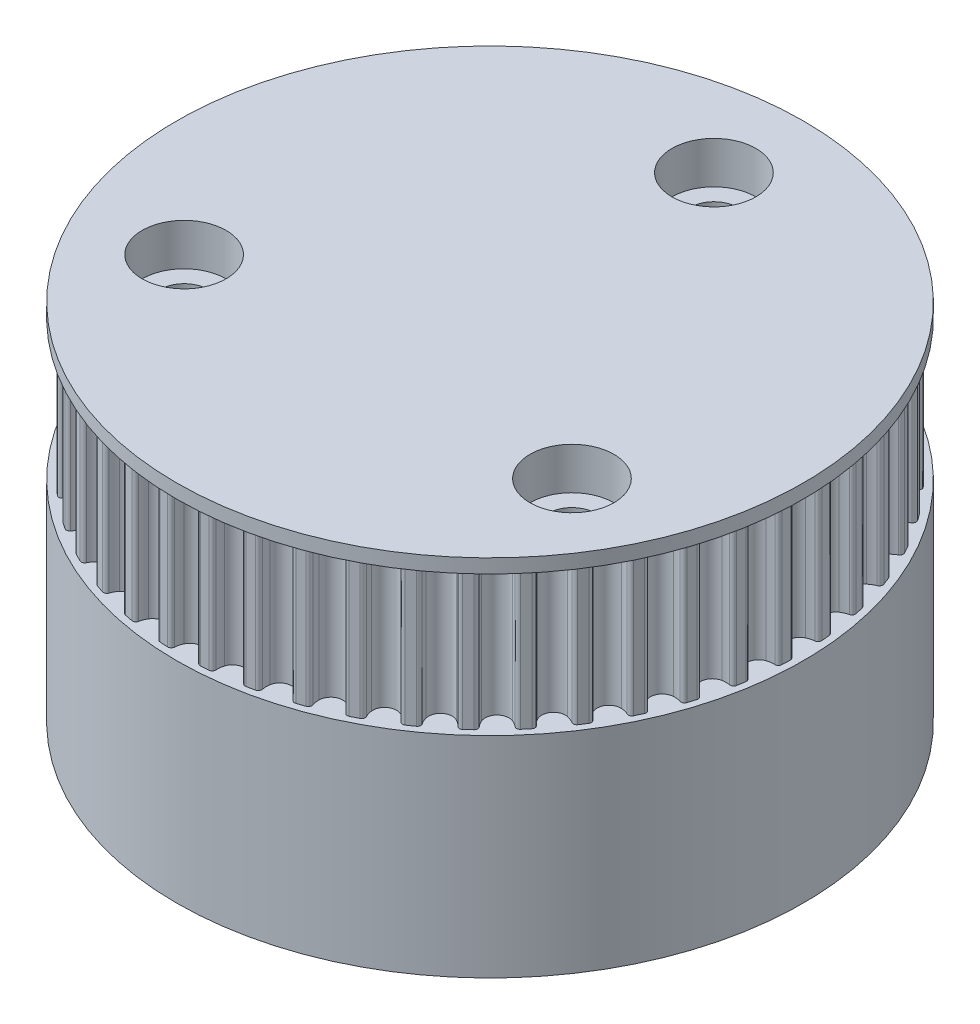
SolidWorks part; units mm, degrees
ref_plane "Front Plane" through (0, 0, 0) normal (0, 0, 1) x (1, 0, 0)
ref_plane "Top Plane" through (0, 0, 0) normal (0, 1, 0) x (1, 0, 0)
ref_plane "Right Plane" through (0, 0, 0) normal (1, 0, 0) x (0, 0, -1)
sketch "Sketch2" plane through (0, 0, 0) normal (0, 1, 0) x (1, 0, 0)
  circle A0 centre (0, 0) radius 21.9
  dimension "D1" = 43.8
extrude "Boss-Extrude1" add sketch "Sketch2" along normal blind 5 and the other way blind 5
sketch "Sketch3" plane through (0, 5, 0) normal (0, 1, 0) x (1, 0, 0)
  line L0 (0, 0) -> (0, 21.9) construction
  line L1 (0, 0) -> (1.4628, 21.8511) construction
  circle A0 centre (0, 0) radius 21.9 construction
  arc A1 (0.2932, 21.898) -> (0, 21.9) centre (0, 0) ccw construction
  arc A2 (0.2932, 21.898) -> (0.5399, 21.6466) centre (0.2899, 21.6481) cw
  arc A3 (0.5399, 21.6466) -> (0.6371, 21.103) centre (2.0598, 21.6379) ccw
  arc A4 (0.6371, 21.103) -> (2.1814, 20.9996) centre (1.4327, 21.4021) ccw
  arc A5 (2.3502, 21.5254) -> (2.1814, 20.9996) centre (0.8426, 21.7194) cw
  arc A6 (2.6281, 21.7417) -> (2.3502, 21.5254) centre (2.5981, 21.4935) ccw
  arc A7 (0.2932, 21.898) -> (2.6281, 21.7417) centre (0, 0) cw
  arc A8 (3.4203, 21.3815) -> (3.4441, 20.8298) centre (4.9255, 21.1703) ccw
  arc A9 (3.2093, 21.6636) -> (3.4203, 21.3815) centre (3.1727, 21.4163) cw
  arc A10 (3.4441, 20.8298) -> (4.9609, 20.5215) centre (4.2725, 21.0202) ccw
  arc A11 (5.1982, 21.0201) -> (4.9609, 20.5215) centre (3.73, 21.4133) cw
  arc A12 (5.5026, 21.1975) -> (5.1982, 21.0201) centre (5.4397, 20.9555) ccw
  arc A13 (3.2093, 21.6636) -> (5.5026, 21.1975) centre (0, 0) cw
  arc A14 (6.2396, 20.7349) -> (6.1897, 20.1849) centre (7.7033, 20.3249) ccw
  arc A15 (6.0682, 21.0425) -> (6.2396, 20.7349) centre (5.9989, 20.8023) cw
  arc A16 (6.1897, 20.1849) -> (7.6519, 19.6772) centre (7.0361, 20.2632) ccw
  arc A17 (7.9536, 20.1397) -> (7.6519, 19.6772) centre (6.5508, 20.725) cw
  arc A18 (8.2788, 20.2749) -> (7.9536, 20.1397) centre (8.1843, 20.0434) ccw
  arc A19 (6.0682, 21.0425) -> (8.2788, 20.2749) centre (0, 0) cw
  arc A20 (8.9476, 19.7182) -> (8.8249, 19.1798) centre (10.3436, 19.1168) ccw
  arc A21 (8.8187, 20.046) -> (8.9476, 19.7182) centre (8.718, 19.8171) cw
  arc A22 (8.8249, 19.1798) -> (10.2063, 18.4817) centre (9.6742, 19.1445) ccw
  arc A23 (10.567, 18.8999) -> (10.2063, 18.4817) centre (9.2547, 19.667) cw
  arc A24 (10.9073, 18.9905) -> (10.567, 18.8999) centre (10.7828, 18.7738) ccw
  arc A25 (8.8187, 20.046) -> (10.9073, 18.9905) centre (0, 0) cw
  arc A26 (11.496, 18.3497) -> (11.3026, 17.8324) centre (12.7993, 17.5675) ccw
  arc A27 (11.4119, 18.6917) -> (11.496, 18.3497) centre (11.2816, 18.4783) cw
  arc A28 (11.3026, 17.8324) -> (12.5786, 16.9564) centre (12.1396, 17.6843) ccw
  arc A29 (12.9918, 17.3228) -> (12.5786, 16.9564) centre (11.7935, 18.258) cw
  arc A30 (13.3412, 17.3673) -> (12.9918, 17.3228) centre (13.1889, 17.169) ccw
  arc A31 (11.4119, 18.6917) -> (13.3412, 17.3673) centre (0, 0) cw
  arc A32 (13.8392, 16.6537) -> (13.5785, 16.1668) centre (15.0266, 15.7048) ccw
  arc A33 (13.8014, 17.0038) -> (13.8392, 16.6537) centre (13.6439, 16.8097) cw
  arc A34 (13.5785, 16.1668) -> (14.7264, 15.1286) centre (14.3883, 15.9084) ccw
  arc A35 (15.1848, 15.4366) -> (14.7264, 15.1286) centre (14.1218, 16.5231) cw
  arc A36 (15.537, 15.4341) -> (15.1848, 15.4366) centre (15.3596, 15.2579) ccw
  arc A37 (13.8014, 17.0038) -> (15.537, 15.4341) centre (0, 0) cw
  arc A38 (15.9354, 14.6605) -> (15.6122, 14.2127) centre (16.9858, 13.5618) ccw
  arc A39 (15.9447, 15.0126) -> (15.9354, 14.6605) centre (15.7627, 14.8412) cw
  arc A40 (15.6122, 14.2127) -> (16.6115, 13.0308) centre (16.3803, 13.8487) ccw
  arc A41 (17.1068, 13.275) -> (16.6115, 13.0308) centre (16.1981, 14.4935) cw
  arc A42 (17.4555, 13.2255) -> (17.1068, 13.275) centre (17.2563, 13.0746) ccw
  arc A43 (15.9447, 15.0126) -> (17.4555, 13.2255) centre (0, 0) cw
  arc A44 (17.7473, 12.4057) -> (17.3673, 12.005) centre (18.6419, 11.1768) ccw
  arc A45 (17.8034, 12.7534) -> (17.7473, 12.4057) centre (17.6002, 12.6078) cw
  arc A46 (17.3673, 12.005) -> (18.2001, 10.7004) centre (18.08, 11.5419) ccw
  arc A47 (18.7235, 10.8764) -> (18.2001, 10.7004) centre (17.9854, 12.2051) cw
  arc A48 (19.0626, 10.7809) -> (18.7235, 10.8764) centre (18.845, 10.6579) ccw
  arc A49 (17.8034, 12.7534) -> (19.0626, 10.7809) centre (0, 0) cw
  arc A50 (19.2425, 9.9295) -> (18.8124, 9.583) centre (19.9653, 8.5924) ccw
  arc A51 (19.3444, 10.2667) -> (19.2425, 9.9295) centre (19.1236, 10.1495) cw
  arc A52 (18.8124, 9.583) -> (19.4639, 8.1791) centre (19.4571, 9.0291) ccw
  arc A53 (20.0062, 8.2838) -> (19.4639, 8.1791) centre (19.4517, 9.699) cw
  arc A54 (20.3294, 8.144) -> (20.0062, 8.2838) centre (20.0974, 8.051) ccw
  arc A55 (19.3444, 10.2667) -> (20.3294, 8.144) centre (0, 0) cw
  arc A56 (20.3942, 7.2762) -> (19.9219, 6.9901) centre (20.9324, 5.8546) ccw
  arc A57 (20.5402, 7.5967) -> (20.3942, 7.2762) centre (20.3057, 7.51) cw
  arc A58 (19.9219, 6.9901) -> (20.3804, 5.5118) centre (20.4869, 6.3551) ccw
  arc A59 (20.9318, 5.5433) -> (20.3804, 5.5118) centre (20.5709, 7.0198) cw
  arc A60 (21.2335, 5.3616) -> (20.9318, 5.5433) centre (20.9911, 5.3004) ccw
  arc A61 (20.5402, 7.5967) -> (21.2335, 5.3616) centre (0, 0) cw
  arc A62 (21.1821, 4.493) -> (20.6758, 4.2724) centre (21.5259, 3.0124) ccw
  arc A63 (21.3695, 4.7912) -> (21.1821, 4.493) centre (21.1255, 4.7365) cw
  arc A64 (20.6758, 4.2724) -> (20.9332, 2.7462) centre (21.1512, 3.5678) ccw
  arc A65 (21.4839, 2.7039) -> (20.9332, 2.7462) centre (21.323, 4.2154) cw
  arc A66 (21.7587, 2.4837) -> (21.4839, 2.7039) centre (21.5103, 2.4553) ccw
  arc A67 (21.3695, 4.7912) -> (21.7587, 2.4837) centre (0, 0) cw
  arc A68 (21.5919, 1.6296) -> (21.0608, 1.4785) centre (21.7354, 0.1164) ccw
  arc A69 (21.8174, 1.9001) -> (21.5919, 1.6296) centre (21.5684, 1.8785) cw
  arc A70 (21.0608, 1.4785) -> (21.1125, -0.0684) centre (21.438, 0.7168) ccw
  arc A71 (21.6526, -0.1837) -> (21.1125, -0.0684) centre (21.6946, 1.3357) cw
  arc A72 (21.8956, -0.4387) -> (21.6526, -0.1837) centre (21.6457, -0.4337) ccw
  arc A73 (21.8174, 1.9001) -> (21.8956, -0.4387) centre (0, 0) cw
  arc A74 (21.6165, -1.2629) -> (21.0699, -1.3419) centre (21.557, -2.7817) ccw
  arc A75 (21.876, -1.0248) -> (21.6165, -1.2629) centre (21.6263, -1.0131) cw
  arc A76 (21.0699, -1.3419) -> (20.915, -2.8819) centre (21.3423, -2.1471) ccw
  arc A77 (21.4349, -3.0681) -> (20.915, -2.8819) centre (21.6791, -1.5679) cw
  arc A78 (21.6418, -3.3531) -> (21.4349, -3.0681) centre (21.3947, -3.3149) ccw
  arc A79 (21.876, -1.0248) -> (21.6418, -3.3531) centre (0, 0) cw
  arc A80 (21.2553, -4.1328) -> (20.7031, -4.1382) centre (20.9938, -5.6302) ccw
  arc A81 (21.5442, -3.9314) -> (21.2553, -4.1328) centre (21.2983, -3.8865) cw
  arc A82 (20.7031, -4.1382) -> (20.3443, -5.6438) centre (20.8657, -4.9725) ccw
  arc A83 (20.8347, -5.8977) -> (20.3443, -5.6438) centre (21.2767, -4.4434) cw
  arc A84 (21.0017, -6.2078) -> (20.8347, -5.8977) centre (20.762, -6.1369) ccw
  arc A85 (21.5442, -3.9314) -> (21.0017, -6.2078) centre (0, 0) cw
  arc A86 (20.5148, -6.929) -> (19.9668, -6.8608) centre (20.0561, -8.3781) ccw
  arc A87 (20.828, -6.7679) -> (20.5148, -6.929) centre (20.5902, -6.6907) cw
  arc A88 (19.9668, -6.8608) -> (19.4105, -8.3051) centre (20.0167, -7.7093) ccw
  arc A89 (19.8627, -8.6221) -> (19.4105, -8.3051) centre (20.4946, -7.2397) cw
  arc A90 (19.9869, -8.9517) -> (19.8627, -8.6221) centre (19.7588, -8.8495) ccw
  arc A91 (20.828, -6.7679) -> (19.9869, -8.9517) centre (0, 0) cw
  arc A92 (19.4082, -9.6015) -> (18.8742, -9.4609) centre (18.7604, -10.9766) ccw
  arc A93 (19.7401, -9.4836) -> (19.4082, -9.6015) centre (19.5147, -9.3754) cw
  arc A94 (18.8742, -9.4609) -> (18.1303, -10.8182) centre (18.8106, -10.3085) ccw
  arc A95 (18.5363, -11.1926) -> (18.1303, -10.8182) centre (19.3468, -9.9067) cw
  arc A96 (18.6155, -11.5358) -> (18.5363, -11.1926) centre (18.403, -11.4041) ccw
  arc A97 (19.7401, -9.4836) -> (18.6155, -11.5358) centre (0, 0) cw
  arc A242 (17.9553, -12.1027) -> (17.4448, -11.8921) centre (17.13, -13.3792) ccw
  arc A243 (18.2999, -12.0301) -> (17.9553, -12.1027) centre (18.091, -11.8928) cw
  arc A244 (17.4448, -11.8921) -> (16.5267, -13.1382) centre (17.2688, -12.7237) ccw
  arc A245 (16.879, -13.5634) -> (16.5267, -13.1382) centre (17.8537, -12.397) cw
  arc A246 (16.9118, -13.9141) -> (16.879, -13.5634) centre (16.7187, -13.7552) ccw
  arc A247 (18.2999, -12.0301) -> (16.9118, -13.9141) centre (0, 0) cw
  arc A248 (16.1819, -14.3879) -> (15.704, -14.1112) centre (15.1939, -15.543) ccw
  arc A249 (16.5332, -14.3619) -> (16.1819, -14.3879) centre (16.3444, -14.198) cw
  arc A250 (15.704, -14.1112) -> (14.628, -15.2237) centre (15.4188, -14.9119) ccw
  arc A251 (14.9206, -15.6921) -> (14.628, -15.2237) centre (16.042, -14.6661) cw
  arc A252 (14.9063, -16.044) -> (14.9206, -15.6921) centre (14.7362, -15.8609) ccw
  arc A253 (16.5332, -14.3619) -> (14.9063, -16.044) centre (0, 0) cw
  arc A254 (14.1198, -16.4164) -> (13.6831, -16.0784) centre (12.9867, -17.4295) ccw
  arc A255 (14.4714, -16.4374) -> (14.1198, -16.4164) centre (14.3062, -16.2498) cw
  arc A256 (13.6831, -16.0784) -> (12.4684, -17.0376) centre (13.2936, -16.8339) ccw
  arc A257 (12.6959, -17.5408) -> (12.4684, -17.0376) centre (13.9441, -16.6734) cw
  arc A258 (12.6349, -17.8877) -> (12.6959, -17.5408) centre (12.4906, -17.6835) ccw
  arc A259 (14.4714, -16.4374) -> (12.6349, -17.8877) centre (0, 0) cw
  arc A260 (11.8057, -18.1519) -> (11.418, -17.7587) centre (10.5477, -19.0049) ccw
  arc A261 (12.1514, -18.2196) -> (11.8057, -18.1519) centre (12.0127, -18.0116) cw
  arc A262 (11.418, -17.7587) -> (10.0863, -18.5475) centre (10.9313, -18.4556) ccw
  arc A263 (10.2447, -19.0765) -> (10.0863, -18.5475) centre (11.5974, -18.3832) cw
  arc A264 (10.1379, -19.4122) -> (10.2447, -19.0765) centre (10.0222, -19.1906) ccw
  arc A265 (12.1514, -18.2196) -> (10.1379, -19.4122) centre (0, 0) cw
  arc A266 (9.281, -19.5635) -> (8.9491, -19.1221) centre (7.9204, -20.2412) ccw
  arc A267 (9.6145, -19.6767) -> (9.281, -19.5635) centre (9.5048, -19.452) cw
  arc A268 (8.9491, -19.1221) -> (7.5241, -19.7264) centre (8.3738, -19.7479) ccw
  arc A269 (7.6106, -20.2718) -> (7.5241, -19.7264) centre (9.0436, -19.7649) cw
  arc A270 (7.4601, -20.5902) -> (7.6106, -20.2718) centre (7.3749, -20.3552) ccw
  arc A271 (9.6145, -19.6767) -> (7.4601, -20.5902) centre (0, 0) cw
  arc A272 (6.5906, -20.626) -> (6.3205, -20.1443) centre (5.1519, -21.1163) ccw
  arc A273 (6.9061, -20.7826) -> (6.5906, -20.626) centre (6.8273, -20.5453) cw
  arc A274 (6.3205, -20.1443) -> (4.8277, -20.5532) centre (5.667, -20.6879) ccw
  arc A275 (4.8408, -21.1053) -> (4.8277, -20.5532) centre (6.3285, -20.794) cw
  arc A276 (4.6491, -21.4008) -> (4.8408, -21.1053) centre (4.5961, -21.1565) ccw
  arc A277 (6.9061, -20.7826) -> (4.6491, -21.4008) centre (0, 0) cw
  arc A278 (3.7826, -21.3204) -> (3.5791, -20.807) centre (2.2914, -21.6146) ccw
  arc A279 (4.0744, -21.5176) -> (3.7826, -21.3204) centre (4.0279, -21.272) cw
  arc A280 (3.5791, -20.807) -> (2.0452, -21.0133) centre (2.859, -21.2586) ccw
  arc A281 (1.9845, -21.5622) -> (2.0452, -21.0133) centre (3.5005, -21.452) cw
  arc A282 (1.7552, -21.8296) -> (1.9845, -21.5622) centre (1.7352, -21.5804) ccw
  arc A283 (4.0744, -21.5176) -> (1.7552, -21.8296) centre (0, 0) cw
  arc A284 (0.9072, -21.6343) -> (0.7739, -21.0984) centre (-0.61, -21.7271) ccw
  arc A285 (1.1701, -21.8687) -> (0.9072, -21.6343) centre (1.1567, -21.6191) cw
  arc A286 (0.7739, -21.0984) -> (-0.7739, -21.0984) centre (0, -21.45) ccw
  arc A287 (-0.9072, -21.6343) -> (-0.7739, -21.0984) centre (0.61, -21.7271) cw
  arc A288 (-1.1701, -21.8687) -> (-0.9072, -21.6343) centre (-1.1567, -21.6191) ccw
  arc A289 (1.1701, -21.8687) -> (-1.1701, -21.8687) centre (0, 0) cw
  arc A290 (-1.9845, -21.5622) -> (-2.0452, -21.0133) centre (-3.5005, -21.452) ccw
  arc A291 (-1.7552, -21.8296) -> (-1.9845, -21.5622) centre (-1.7352, -21.5804) cw
  arc A292 (-2.0452, -21.0133) -> (-3.5791, -20.807) centre (-2.859, -21.2586) ccw
  arc A293 (-3.7826, -21.3204) -> (-3.5791, -20.807) centre (-2.2914, -21.6146) cw
  arc A294 (-4.0744, -21.5176) -> (-3.7826, -21.3204) centre (-4.0279, -21.272) ccw
  arc A295 (-1.7552, -21.8296) -> (-4.0744, -21.5176) centre (0, 0) cw
  arc A296 (-4.8408, -21.1053) -> (-4.8277, -20.5532) centre (-6.3285, -20.794) ccw
  arc A297 (-4.6491, -21.4008) -> (-4.8408, -21.1053) centre (-4.5961, -21.1565) cw
  arc A298 (-4.8277, -20.5532) -> (-6.3205, -20.1443) centre (-5.667, -20.6879) ccw
  arc A299 (-6.5906, -20.626) -> (-6.3205, -20.1443) centre (-5.1519, -21.1163) cw
  arc A300 (-6.9061, -20.7826) -> (-6.5906, -20.626) centre (-6.8273, -20.5453) ccw
  arc A301 (-4.6491, -21.4008) -> (-6.9061, -20.7826) centre (0, 0) cw
  arc A302 (-7.6106, -20.2718) -> (-7.5241, -19.7264) centre (-9.0436, -19.7649) ccw
  arc A303 (-7.4601, -20.5902) -> (-7.6106, -20.2718) centre (-7.3749, -20.3552) cw
  arc A304 (-7.5241, -19.7264) -> (-8.9491, -19.1221) centre (-8.3738, -19.7479) ccw
  arc A305 (-9.281, -19.5635) -> (-8.9491, -19.1221) centre (-7.9204, -20.2412) cw
  arc A306 (-9.6145, -19.6767) -> (-9.281, -19.5635) centre (-9.5048, -19.452) ccw
  arc A307 (-7.4601, -20.5902) -> (-9.6145, -19.6767) centre (0, 0) cw
  arc A308 (-10.2447, -19.0765) -> (-10.0863, -18.5475) centre (-11.5974, -18.3832) ccw
  arc A309 (-10.1379, -19.4122) -> (-10.2447, -19.0765) centre (-10.0222, -19.1906) cw
  arc A310 (-10.0863, -18.5475) -> (-11.418, -17.7587) centre (-10.9313, -18.4556) ccw
  arc A311 (-11.8057, -18.1519) -> (-11.418, -17.7587) centre (-10.5477, -19.0049) cw
  arc A312 (-12.1514, -18.2196) -> (-11.8057, -18.1519) centre (-12.0127, -18.0116) ccw
  arc A313 (-10.1379, -19.4122) -> (-12.1514, -18.2196) centre (0, 0) cw
  arc A314 (-12.6959, -17.5408) -> (-12.4684, -17.0376) centre (-13.9441, -16.6734) ccw
  arc A315 (-12.6349, -17.8877) -> (-12.6959, -17.5408) centre (-12.4906, -17.6835) cw
  arc A316 (-12.4684, -17.0376) -> (-13.6831, -16.0784) centre (-13.2936, -16.8339) ccw
  arc A317 (-14.1198, -16.4164) -> (-13.6831, -16.0784) centre (-12.9867, -17.4295) cw
  arc A318 (-14.4714, -16.4374) -> (-14.1198, -16.4164) centre (-14.3062, -16.2498) ccw
  arc A319 (-12.6349, -17.8877) -> (-14.4714, -16.4374) centre (0, 0) cw
  arc A320 (-14.9206, -15.6921) -> (-14.628, -15.2237) centre (-16.042, -14.6661) ccw
  arc A321 (-14.9063, -16.044) -> (-14.9206, -15.6921) centre (-14.7362, -15.8609) cw
  arc A322 (-14.628, -15.2237) -> (-15.704, -14.1112) centre (-15.4188, -14.9119) ccw
  arc A323 (-16.1819, -14.3879) -> (-15.704, -14.1112) centre (-15.1939, -15.543) cw
  arc A324 (-16.5332, -14.3619) -> (-16.1819, -14.3879) centre (-16.3444, -14.198) ccw
  arc A325 (-14.9063, -16.044) -> (-16.5332, -14.3619) centre (0, 0) cw
  arc A338 (-16.879, -13.5634) -> (-16.5267, -13.1382) centre (-17.8537, -12.397) ccw
  arc A339 (-16.9118, -13.9141) -> (-16.879, -13.5634) centre (-16.7187, -13.7552) cw
  arc A340 (-16.5267, -13.1382) -> (-17.4448, -11.8921) centre (-17.2688, -12.7237) ccw
  arc A341 (-17.9553, -12.1027) -> (-17.4448, -11.8921) centre (-17.13, -13.3792) cw
  arc A342 (-18.2999, -12.0301) -> (-17.9553, -12.1027) centre (-18.091, -11.8928) ccw
  arc A343 (-16.9118, -13.9141) -> (-18.2999, -12.0301) centre (0, 0) cw
  arc A344 (-18.5363, -11.1926) -> (-18.1303, -10.8182) centre (-19.3468, -9.9067) ccw
  arc A345 (-18.6155, -11.5358) -> (-18.5363, -11.1926) centre (-18.403, -11.4041) cw
  arc A346 (-18.1303, -10.8182) -> (-18.8742, -9.4609) centre (-18.8106, -10.3085) ccw
  arc A347 (-19.4082, -9.6015) -> (-18.8742, -9.4609) centre (-18.7604, -10.9766) cw
  arc A348 (-19.7401, -9.4836) -> (-19.4082, -9.6015) centre (-19.5147, -9.3754) ccw
  arc A349 (-18.6155, -11.5358) -> (-19.7401, -9.4836) centre (0, 0) cw
  arc A350 (-19.8627, -8.6221) -> (-19.4105, -8.3051) centre (-20.4946, -7.2397) ccw
  arc A351 (-19.9869, -8.9517) -> (-19.8627, -8.6221) centre (-19.7588, -8.8495) cw
  arc A352 (-19.4105, -8.3051) -> (-19.9668, -6.8608) centre (-20.0167, -7.7093) ccw
  arc A353 (-20.5148, -6.929) -> (-19.9668, -6.8608) centre (-20.0561, -8.3781) cw
  arc A354 (-20.828, -6.7679) -> (-20.5148, -6.929) centre (-20.5902, -6.6907) ccw
  arc A355 (-19.9869, -8.9517) -> (-20.828, -6.7679) centre (0, 0) cw
  arc A356 (-20.8347, -5.8977) -> (-20.3443, -5.6438) centre (-21.2767, -4.4434) ccw
  arc A357 (-21.0017, -6.2078) -> (-20.8347, -5.8977) centre (-20.762, -6.1369) cw
  arc A358 (-20.3443, -5.6438) -> (-20.7031, -4.1382) centre (-20.8657, -4.9725) ccw
  arc A359 (-21.2553, -4.1328) -> (-20.7031, -4.1382) centre (-20.9938, -5.6302) cw
  arc A360 (-21.5442, -3.9314) -> (-21.2553, -4.1328) centre (-21.2983, -3.8865) ccw
  arc A361 (-21.0017, -6.2078) -> (-21.5442, -3.9314) centre (0, 0) cw
  arc A362 (-21.4349, -3.0681) -> (-20.915, -2.8819) centre (-21.6791, -1.5679) ccw
  arc A363 (-21.6418, -3.3531) -> (-21.4349, -3.0681) centre (-21.3947, -3.3149) cw
  arc A364 (-20.915, -2.8819) -> (-21.0699, -1.3419) centre (-21.3423, -2.1471) ccw
  arc A365 (-21.6165, -1.2629) -> (-21.0699, -1.3419) centre (-21.557, -2.7817) cw
  arc A366 (-21.876, -1.0248) -> (-21.6165, -1.2629) centre (-21.6263, -1.0131) ccw
  arc A367 (-21.6418, -3.3531) -> (-21.876, -1.0248) centre (0, 0) cw
  arc A368 (-21.6526, -0.1837) -> (-21.1125, -0.0684) centre (-21.6946, 1.3357) ccw
  arc A369 (-21.8956, -0.4387) -> (-21.6526, -0.1837) centre (-21.6457, -0.4337) cw
  arc A370 (-21.1125, -0.0684) -> (-21.0608, 1.4785) centre (-21.438, 0.7168) ccw
  arc A371 (-21.5919, 1.6296) -> (-21.0608, 1.4785) centre (-21.7354, 0.1164) cw
  arc A372 (-21.8174, 1.9001) -> (-21.5919, 1.6296) centre (-21.5684, 1.8785) ccw
  arc A373 (-21.8956, -0.4387) -> (-21.8174, 1.9001) centre (0, 0) cw
  arc A374 (-21.4839, 2.7039) -> (-20.9332, 2.7462) centre (-21.323, 4.2154) ccw
  arc A375 (-21.7587, 2.4837) -> (-21.4839, 2.7039) centre (-21.5103, 2.4553) cw
  arc A376 (-20.9332, 2.7462) -> (-20.6758, 4.2724) centre (-21.1512, 3.5678) ccw
  arc A377 (-21.1821, 4.493) -> (-20.6758, 4.2724) centre (-21.5259, 3.0124) cw
  arc A378 (-21.3695, 4.7912) -> (-21.1821, 4.493) centre (-21.1255, 4.7365) ccw
  arc A379 (-21.7587, 2.4837) -> (-21.3695, 4.7912) centre (0, 0) cw
  arc A380 (-20.9318, 5.5433) -> (-20.3804, 5.5118) centre (-20.5709, 7.0198) ccw
  arc A381 (-21.2335, 5.3616) -> (-20.9318, 5.5433) centre (-20.9911, 5.3004) cw
  arc A382 (-20.3804, 5.5118) -> (-19.9219, 6.9901) centre (-20.4869, 6.3551) ccw
  arc A383 (-20.3942, 7.2762) -> (-19.9219, 6.9901) centre (-20.9324, 5.8546) cw
  arc A384 (-20.5402, 7.5967) -> (-20.3942, 7.2762) centre (-20.3057, 7.51) ccw
  arc A385 (-21.2335, 5.3616) -> (-20.5402, 7.5967) centre (0, 0) cw
  arc A386 (-20.0062, 8.2838) -> (-19.4639, 8.1791) centre (-19.4517, 9.699) ccw
  arc A387 (-20.3294, 8.144) -> (-20.0062, 8.2838) centre (-20.0974, 8.051) cw
  arc A388 (-19.4639, 8.1791) -> (-18.8124, 9.583) centre (-19.4571, 9.0291) ccw
  arc A389 (-19.2425, 9.9295) -> (-18.8124, 9.583) centre (-19.9653, 8.5924) cw
  arc A390 (-19.3444, 10.2667) -> (-19.2425, 9.9295) centre (-19.1236, 10.1495) ccw
  arc A391 (-20.3294, 8.144) -> (-19.3444, 10.2667) centre (0, 0) cw
  arc A392 (-18.7235, 10.8764) -> (-18.2001, 10.7004) centre (-17.9854, 12.2051) ccw
  arc A393 (-19.0626, 10.7809) -> (-18.7235, 10.8764) centre (-18.845, 10.6579) cw
  arc A394 (-18.2001, 10.7004) -> (-17.3673, 12.005) centre (-18.08, 11.5419) ccw
  arc A395 (-17.7473, 12.4057) -> (-17.3673, 12.005) centre (-18.6419, 11.1768) cw
  arc A396 (-17.8034, 12.7534) -> (-17.7473, 12.4057) centre (-17.6002, 12.6078) ccw
  arc A397 (-19.0626, 10.7809) -> (-17.8034, 12.7534) centre (0, 0) cw
  arc A398 (-17.1068, 13.275) -> (-16.6115, 13.0308) centre (-16.1981, 14.4935) ccw
  arc A399 (-17.4555, 13.2255) -> (-17.1068, 13.275) centre (-17.2563, 13.0746) cw
  arc A400 (-16.6115, 13.0308) -> (-15.6122, 14.2127) centre (-16.3803, 13.8487) ccw
  arc A401 (-15.9354, 14.6605) -> (-15.6122, 14.2127) centre (-16.9858, 13.5618) cw
  arc A402 (-15.9447, 15.0126) -> (-15.9354, 14.6605) centre (-15.7627, 14.8412) ccw
  arc A403 (-17.4555, 13.2255) -> (-15.9447, 15.0126) centre (0, 0) cw
  arc A404 (-15.1848, 15.4366) -> (-14.7264, 15.1286) centre (-14.1218, 16.5231) ccw
  arc A405 (-15.537, 15.4341) -> (-15.1848, 15.4366) centre (-15.3596, 15.2579) cw
  arc A406 (-14.7264, 15.1286) -> (-13.5785, 16.1668) centre (-14.3883, 15.9084) ccw
  arc A407 (-13.8392, 16.6537) -> (-13.5785, 16.1668) centre (-15.0266, 15.7048) cw
  arc A408 (-13.8014, 17.0038) -> (-13.8392, 16.6537) centre (-13.6439, 16.8097) ccw
  arc A409 (-15.537, 15.4341) -> (-13.8014, 17.0038) centre (0, 0) cw
  arc A410 (-12.9918, 17.3228) -> (-12.5786, 16.9564) centre (-11.7935, 18.258) ccw
  arc A411 (-13.3412, 17.3673) -> (-12.9918, 17.3228) centre (-13.1889, 17.169) cw
  arc A412 (-12.5786, 16.9564) -> (-11.3026, 17.8324) centre (-12.1396, 17.6843) ccw
  arc A413 (-11.496, 18.3497) -> (-11.3026, 17.8324) centre (-12.7993, 17.5675) cw
  arc A414 (-11.4119, 18.6917) -> (-11.496, 18.3497) centre (-11.2816, 18.4783) ccw
  arc A415 (-13.3412, 17.3673) -> (-11.4119, 18.6917) centre (0, 0) cw
  arc A416 (-10.567, 18.8999) -> (-10.2063, 18.4817) centre (-9.2547, 19.667) ccw
  arc A417 (-10.9073, 18.9905) -> (-10.567, 18.8999) centre (-10.7828, 18.7738) cw
  arc A418 (-10.2063, 18.4817) -> (-8.8249, 19.1798) centre (-9.6742, 19.1445) ccw
  arc A419 (-8.9476, 19.7182) -> (-8.8249, 19.1798) centre (-10.3436, 19.1168) cw
  arc A420 (-8.8187, 20.046) -> (-8.9476, 19.7182) centre (-8.718, 19.8171) ccw
  arc A421 (-10.9073, 18.9905) -> (-8.8187, 20.046) centre (0, 0) cw
  arc A434 (-7.9536, 20.1397) -> (-7.6519, 19.6772) centre (-6.5508, 20.725) ccw
  arc A435 (-8.2788, 20.2749) -> (-7.9536, 20.1397) centre (-8.1843, 20.0434) cw
  arc A436 (-7.6519, 19.6772) -> (-6.1897, 20.1849) centre (-7.0361, 20.2632) ccw
  arc A437 (-6.2396, 20.7349) -> (-6.1897, 20.1849) centre (-7.7033, 20.3249) cw
  arc A438 (-6.0682, 21.0425) -> (-6.2396, 20.7349) centre (-5.9989, 20.8023) ccw
  arc A439 (-8.2788, 20.2749) -> (-6.0682, 21.0425) centre (0, 0) cw
  arc A440 (-5.1982, 21.0201) -> (-4.9609, 20.5215) centre (-3.73, 21.4133) ccw
  arc A441 (-5.5026, 21.1975) -> (-5.1982, 21.0201) centre (-5.4397, 20.9555) cw
  arc A442 (-4.9609, 20.5215) -> (-3.4441, 20.8298) centre (-4.2725, 21.0202) ccw
  arc A443 (-3.4203, 21.3815) -> (-3.4441, 20.8298) centre (-4.9255, 21.1703) cw
  arc A444 (-3.2093, 21.6636) -> (-3.4203, 21.3815) centre (-3.1727, 21.4163) ccw
  arc A445 (-5.5026, 21.1975) -> (-3.2093, 21.6636) centre (0, 0) cw
  arc A446 (-2.3502, 21.5254) -> (-2.1814, 20.9996) centre (-0.8426, 21.7194) ccw
  arc A447 (-2.6281, 21.7417) -> (-2.3502, 21.5254) centre (-2.5981, 21.4935) cw
  arc A448 (-2.1814, 20.9996) -> (-0.6371, 21.103) centre (-1.4327, 21.4021) ccw
  arc A449 (-0.5399, 21.6466) -> (-0.6371, 21.103) centre (-2.0598, 21.6379) cw
  arc A450 (-0.2932, 21.898) -> (-0.5399, 21.6466) centre (-0.2899, 21.6481) ccw
  arc A451 (-2.6281, 21.7417) -> (-0.2932, 21.898) centre (0, 0) cw
  point P18 (1.3759, 20.554)
  point P202 (0, 0)
  dimension "D2" = 0.25
  dimension "D3" = 1.52
  dimension "D5" = 0.85
  dimension "D1" = 3.83
  dimension "D4" = 0.61
  dimension "D6" = 1.3
  dimension "D7" = 47
extrude "Cut-Extrude1" cut sketch "Sketch3" against normal up to surface (10 mm away) up to face at (0, -5, 21.9)
sketch "Sketch4" plane through (0, -5, 0) normal (0, -1, 0) x (1, 0, 0)
  circle A0 centre (0, 0) radius 22.4
  dimension "D1" = 44.8
extrude "Boss-Extrude2" add sketch "Sketch4" along normal blind 1
mirror "Mirror1" about plane through (0, 0, 0) normal (0, 1, 0) of "Boss-Extrude2"
sketch "Sketch9" [suppressed] plane through (0, 6, 0) normal (0, 1, 0) x (1, 0, 0)
  line L0 (0, 0) -> (0, 16) construction
  arc A0 (0.2932, 21.898) -> (-0.2932, 21.898) centre (0, 0) ccw construction
  arc A1 (0.2932, 21.898) -> (-0.2932, 21.898) centre (0, 0) ccw construction
  circle A2 centre (0, 16) radius 1.7
  circle A3 centre (16, 0) radius 1.7
  circle A4 centre (0, -16) radius 1.7
  circle A5 centre (-16, 0) radius 1.7
  point P16 (0, 0)
  dimension "D1" = 3.4
  dimension "D2" = 16
  dimension "D3" = 4
extrude "Cut-Extrude4" [suppressed] cut sketch "Sketch9" against normal through all
sketch "Sketch10" [suppressed] plane through (0, -6, 0) normal (0, -1, 0) x (1, 0, 0)
  circle A0 centre (0, 0) radius 10.5
  dimension "D1" = 21
extrude "Cut-Extrude5" [suppressed] cut sketch "Sketch10" against normal through all
sketch "Sketch11" plane through (0, 6, 0) normal (0, 1, 0) x (1, 0, 0)
  line L0 (0, 0) -> (0, 16) construction
  circle A0 centre (0, 16) radius 1.7
  circle A1 centre (13.8564, -8) radius 1.7
  circle A2 centre (-13.8564, -8) radius 1.7
  point P10 (0, 0)
  dimension "D1" = 3.4
  dimension "D2" = 16
  dimension "D3" = 3
extrude "Cut-Extrude6" cut sketch "Sketch11" against normal through all
sketch "Sketch12" plane through (0, -6, 0) normal (0, -1, 0) x (1, 0, 0)
  circle A0 centre (0, -16) radius 1.7 construction
  circle A1 centre (0, 0) radius 22.4
  circle A2 centre (0, 0) radius 22.4
  circle A3 centre (13.8564, 8) radius 1.7 construction
  circle A4 centre (-13.8564, 8) radius 1.7 construction
  circle A5 centre (0, -16) radius 1.7
  circle A6 centre (13.8564, 8) radius 1.7
  circle A7 centre (-13.8564, 8) radius 1.7
  dimension "D1" = 0
extrude "Boss-Extrude3" add sketch "Sketch12" along normal blind 14
sketch "Sketch13" plane through (0, -20, 0) normal (0, -1, 0) x (1, 0, 0)
  line L0 (0, 0) -> (0, 20) construction
  line L1 (-16.4125, 12.9399) -> (0, 3.4641)
  line L2 (-13.8564, 8) -> (0, 0) construction
  line L3 (16.4125, 12.9399) -> (0, 3.4641)
  line L4 (3, -20.6836) -> (3, -1.7321)
  line L5 (19.4125, 7.7437) -> (3, -1.7321)
  line L6 (-19.4125, 7.7437) -> (-3, -1.7321)
  line L7 (-3, -20.6836) -> (-3, -1.7321)
  arc A0 (-16.4125, 12.9399) -> (16.4125, 12.9399) centre (0, 0) cw
  arc A1 (19.4125, 7.7437) -> (3, -20.6836) centre (0, 0) cw
  arc A2 (-3, -20.6836) -> (-19.4125, 7.7437) centre (0, 0) cw
  point P17 (0, 0)
  dimension "D2" = 20.9
  dimension "D1" = 3
  dimension "D3" = 3
extrude "Cut-Extrude7" cut sketch "Sketch13" against normal offset from surface (14.5 mm away) 0.5 up to face at (0, -5, 0)
chamfer "Chamfer1" distance 7 angle 30 9 edges at (8.2062, -5.5, 8.202) (-8.2062, -5.5, 8.202) (0, -5.5, 20.9) (3, -5.5, -11.2078) (11.2062, -5.5, 3.0058) (18.0999, -5.5, -10.45) (-11.2062, -5.5, 3.0058) (-3, -5.5, -11.2078) (-18.0999, -5.5, -10.45) first distance on face at (0, -5.5, 12.4347) first distance on face at (10.7687, -5.5, -6.2173) first distance on face at (-10.7687, -5.5, -6.2173)
sketch "Sketch14" plane through (0, 6, 0) normal (0, 1, 0) x (1, 0, 0)
  circle A0 centre (-13.8564, -8) radius 3
  circle A1 centre (0, 16) radius 3
  circle A2 centre (13.8564, -8) radius 3
  dimension "D1" = 6
extrude "Cut-Extrude8" cut sketch "Sketch14" against normal blind 3
equation "\"teeth\"= 47"
equation "\"pitchdiameter\"= \"teeth\" - 3.2"
equation "\"teethangle\"= 360 / \"teeth\""
equation "\"D1@Sketch2\"=\"pitchdiameter\""
equation "\"D1@Sketch3\"=\"teethangle\"/2"
equation "\"D7@Sketch3\"=\"teeth\""
equation "\"D1@Sketch4\"=\"pitchdiameter\" + 1"
equation "\"pitch\"= 2"
equation "\"D2@Sketch13\"=\"pitchdiameter\"/2 - 1"
